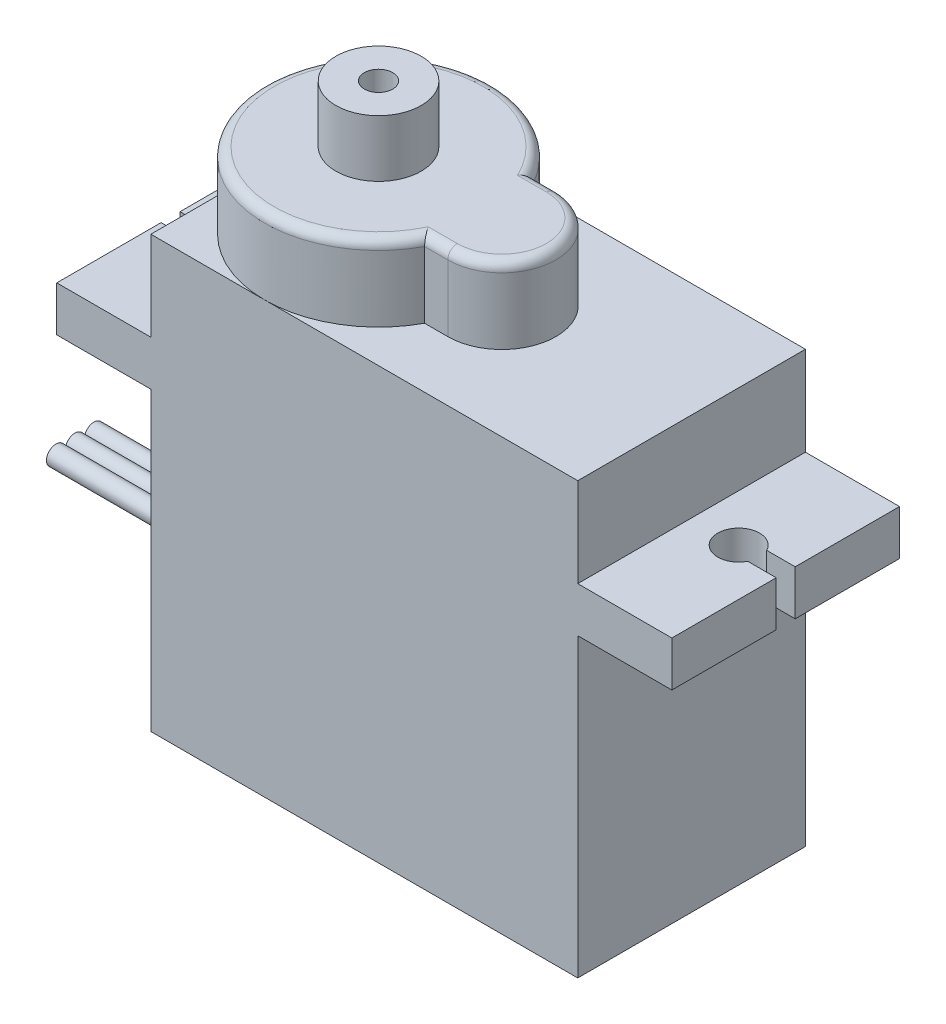
SolidWorks part; units mm, degrees
ref_plane "Plano frontal" through (0, 0, 0) normal (0, 0, 1) x (1, 0, 0)
ref_plane "Plano superior" through (0, 0, 0) normal (0, 1, 0) x (1, 0, 0)
ref_plane "Plano direito" through (0, 0, 0) normal (1, 0, 0) x (0, 0, -1)
sketch "Esboço1" plane through (0, 0, 0) normal (0, 1, 0) x (1, 0, 0)
  line L1 (-11.25, 6) -> (11.25, 6)
  line L2 (-11.25, 6) -> (-11.25, -6)
  line L3 (-11.25, -6) -> (11.25, -6)
  line L4 (11.25, 6) -> (11.25, -6)
  line L5 (-11.25, 6) -> (11.25, -6) construction
  line L6 (-11.25, -6) -> (11.25, 6) construction
  point P0 (0, 0)
  dimension "D1" = 12
  dimension "D2" = 22.5
extrude "Body" add sketch "Esboço1" along normal blind 4.7 and the other way blind 18
sketch "Esboço2" plane through (0, 0, 0) normal (0, 1, 0) x (1, 0, 0)
  line L0 (-11.25, -6) -> (11.25, -6) construction
  line L1 (-11.25, 6) -> (-16.21, 6)
  line L2 (-11.25, 6) -> (-11.25, -6)
  line L3 (-11.25, -6) -> (-16.21, -6)
  line L4 (-16.21, 6) -> (-16.21, 0.5)
  line L5 (11.25, 6) -> (16.21, 6)
  line L6 (11.25, 6) -> (11.25, -6)
  line L7 (11.25, -6) -> (16.21, -6)
  line L8 (16.21, 6) -> (16.21, 0.5)
  line L9 (-16.21, -0.5) -> (-16.21, -6)
  line L10 (-16.21, 0.5) -> (-14.9548, 0.5)
  line L11 (16.21, -0.5) -> (16.21, -6)
  line L12 (-16.21, -0.5) -> (-14.9548, -0.5)
  line L14 (16.21, 0.5) -> (14.7098, 0.5)
  line L16 (16.21, -0.5) -> (14.7098, -0.5)
  arc A0 (-14.9548, -0.5) -> (-14.9548, 0.5) centre (-13.975, 0) ccw
  arc A1 (14.7098, 0.5) -> (14.7098, -0.5) centre (13.73, 0) ccw
  point P18 (13.73, 6)
  dimension "D2" = 2.2
  dimension "D3" = 1
  dimension "D4" = 1
  dimension "D1" = 13.975
  dimension "D5" = 16.21
extrude "tabs" add sketch "Esboço2" against normal blind 2.375
sketch "Esboço3" plane through (0, 4.7, 0) normal (0, 1, 0) x (1, 0, 0)
  line L0 (-11.25, -6) -> (-11.25, 6) construction
  line L1 (11.25, 6) -> (-11.25, 6) construction
  line L2 (-11.25, -6) -> (11.25, -6) construction
  line L3 (0.75, 0) -> (1.25, 0) construction
  line L4 (0.0299, 2.85) -> (1.25, 2.85)
  line L5 (0.0299, -2.85) -> (1.25, -2.85)
  line L6 (11.25, -6) -> (11.25, 6) construction
  arc A0 (0.0299, 2.85) -> (0.0299, -2.85) centre (-5.25, 0) ccw
  arc A2 (1.25, -2.85) -> (1.25, 2.85) centre (1.25, 0) ccw
  point P10 (-1.7695, 0)
  dimension "D2" = 5.7
  dimension "D1" = 10
extrude "Top Gear Housing" add sketch "Esboço3" along normal blind 4
sketch "Esboço4" plane through (0, 8.7, 0) normal (0, 1, 0) x (1, 0, 0)
  circle A0 centre (-5.25, 0) radius 2.25
  arc A1 (0.0299, 2.85) -> (0.0299, -2.85) centre (-5.25, 0) ccw construction
  dimension "D1" = 4.5
extrude "shaft" add sketch "Esboço4" along normal blind 3
sketch "Esboço5" plane through (0, 11.7, 0) normal (0, 1, 0) x (1, 0, 0)
  circle A0 centre (-5.25, 0) radius 0.75
  dimension "D1" = 1.5
extrude "shaft hole" cut sketch "Esboço5" against normal blind 5
fillet "Filete2" radius 0.5 4 edges at (0.64, 8.7, 2.85) (0.64, 8.7, -2.85) (4.1, 8.7, 0) (-11.25, 8.7, 0)
ref_axis "Axis1" through (-5.25, 11.7, 0) along (0, -1, 0)
sketch "Sketch1" plane through (-11.25, 0, 0) normal (-1, 0, 0) x (0, 0, 1)
  line L0 (0, 0) -> (0, -18) construction
  line L1 (-6, -18) -> (6, -18) construction
  line L2 (-6, -2.375) -> (-0.5, -2.375) construction
  circle A0 centre (-1, -12.875) radius 0.5
  point P7 (-1, -12.375)
  dimension "D2" = 1
  dimension "D1" = 2
  dimension "D3" = 10
extrude "Boss-Extrude1" add sketch "Sketch1" along normal blind 10
pattern_linear "LPattern2" count 3 spacing 1.001 along (0, 0, 1) of "Boss-Extrude1"
equation "\"D1@Esboço2\"=27.95/2"
equation "\"D5@Esboço2\"=32.42/2"
